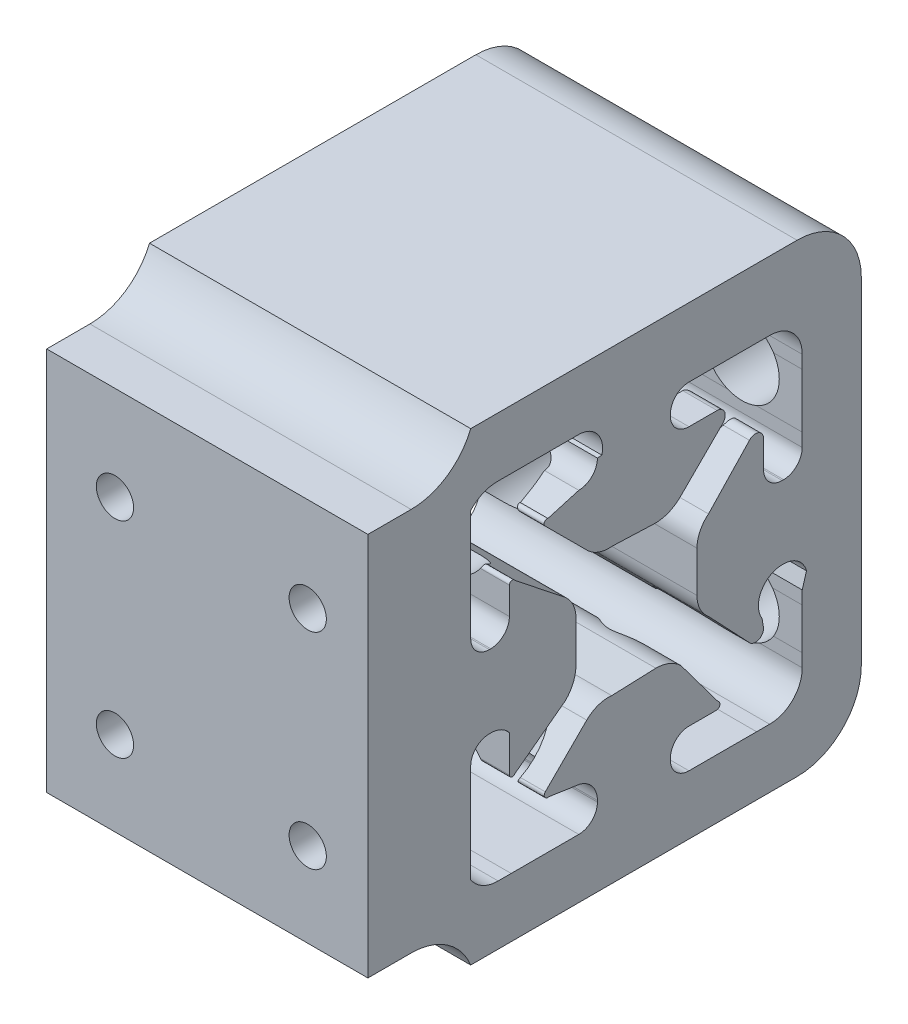
SolidWorks part; units mm, degrees
ref_plane "Front Plane" through (0, 0, 0) normal (0, 0, 1) x (1, 0, 0)
ref_plane "Top Plane" through (0, 0, 0) normal (0, 1, 0) x (1, 0, 0)
ref_plane "Right Plane" through (0, 0, 0) normal (1, 0, 0) x (0, 0, -1)
sketch "Sketch1" plane through (0, 0, 0) normal (0, 0, 1) x (1, 0, 0)
  line L1 (-7.5, -8) -> (7.5, -8) construction
  line L2 (-7.5, -8) -> (-7.5, 8) construction
  line L3 (-7.5, 8) -> (7.5, 8) construction
  line L4 (7.5, -8) -> (7.5, 8) construction
  line L5 (-7.5, -8) -> (7.5, 8) construction
  line L6 (-7.5, 8) -> (7.5, -8) construction
  line L7 (-12.8154, -14.5728) -> (12.1846, -14.5728)
  line L8 (-12.8154, -14.5728) -> (-12.8154, 15.3272)
  line L9 (-12.8154, 15.3272) -> (12.1846, 15.3272)
  line L10 (12.1846, -14.5728) -> (12.1846, 15.3272)
  line L11 (-12.8154, -14.5728) -> (12.1846, 15.3272) construction
  line L12 (-12.8154, 15.3272) -> (12.1846, -14.5728) construction
  circle A0 centre (-7.5, 8) radius 2.9
  circle A1 centre (7.5, 8) radius 2.9
  circle A2 centre (7.5, -8) radius 2.9
  circle A3 centre (-7.5, -8) radius 2.9
  point P0 (0, 0)
  point P6 (0, 0)
  dimension "D3" = 5.8
  dimension "D1" = 16
  dimension "D2" = 15
  dimension "D6" = 29.9
  dimension "D7" = 25
  dimension "D8" = 5.3154
  dimension "D4" = 2
  dimension "D5" = 2
extrude "Boss-Extrude1" add sketch "Sketch1" along normal blind 5
sketch "Sketch2" plane through (0, 0, 0) normal (1, 0, 0) x (0, 0, -1)
  line L0 (5.5203, -8.6452) -> (8.7477, -5.4237) construction
  line L1 (10.9895, -4.627) -> (14.4013, -4.4958) construction
  line L2 (16.6734, -5.445) -> (19.5306, -9.27) construction
  line L3 (19.1164, -10.4902) -> (16.9875, -10.4902) construction
  line L4 (15.9385, -11.5392) -> (15.9385, -11.651) construction
  line L5 (16.9875, -12.7) -> (18.0171, -12.7) construction
  line L6 (19.0331, -12.7) -> (22.2504, -12.7) construction
  line L7 (25.4, -9.5504) -> (25.4, -6.3331) construction
  line L8 (25.4, -5.2589) -> (25.7151, -4.1987) construction
  line L9 (24.351, -3.2385) -> (24.2392, -3.2385) construction
  line L10 (23.0637, -5.5347) -> (23.1538, -6.131) construction
  line L11 (21.4013, -7.0918) -> (18.2348, -3.7479) construction
  line L12 (17.2085, -1.5932) -> (17.2085, 1.5932) construction
  line L13 (18.2348, 3.7479) -> (21.4013, 7.0918) construction
  line L14 (23.1902, 6.4021) -> (23.1902, 4.2875) construction
  line L15 (24.2392, 3.2385) -> (24.351, 3.2385) construction
  line L16 (25.4, 4.2875) -> (25.4, 5.3171) construction
  line L17 (25.4, 6.3331) -> (25.4, 9.5504) construction
  line L18 (22.2504, 12.7) -> (19.0331, 12.7) construction
  line L19 (18.0171, 12.7) -> (16.9875, 12.7) construction
  line L20 (15.9385, 11.651) -> (15.9385, 11.5392) construction
  line L21 (16.9875, 10.4902) -> (19.1768, 10.4902) construction
  line L22 (19.907, 8.7244) -> (16.5983, 5.4232) construction
  line L23 (14.1125, 4.5051) -> (11.0428, 4.6269) construction
  line L24 (8.8017, 5.4232) -> (5.493, 8.7244) construction
  line L25 (5.9838, 9.8056) -> (8.3604, 10.4915) construction
  line L26 (9.3959, 11.9043) -> (9.86, 11.9403) construction
  line L27 (8.4125, 13.4545) -> (7.3829, 13.4545) construction
  line L28 (6.3669, 13.4545) -> (3.1497, 13.4545) construction
  line L31 (1.449, 3.2385) -> (1.5608, 3.2385) construction
  line L32 (2.6098, 4.2875) -> (2.6098, 6.4021) construction
  line L33 (3.7361, 6.7825) -> (7.54, 3.7681) construction
  line L34 (8.5915, 1.5932) -> (8.5915, -1.5932) construction
  line L35 (7.6385, -3.8611) -> (3.7076, -6.8173) construction
  line L36 (2.6098, -6.4021) -> (2.6098, -3.6879) construction
  line L37 (1.5608, -3.2385) -> (1.449, -3.2385) construction
  line L40 (3.1496, -12.7) -> (6.3669, -12.7) construction
  line L41 (7.3829, -12.7) -> (8.4125, -12.7) construction
  line L42 (9.4615, -11.651) -> (9.4615, -11.5392) construction
  line L43 (8.42, -10.1487) -> (6.0885, -9.8015) construction
  line L44 (0, 0) -> (36.6961, 0) construction
  line L45 (0, -14.5728) -> (0, 15.3272) construction
  line L46 (0, -14.5728) -> (0, -11.9507)
  line L47 (0, 15.3272) -> (0, 18.4545)
  line L48 (0, 18.4545) -> (30.4, 18.4545)
  line L49 (30.4, 18.4545) -> (30.4, -17.7)
  line L50 (30.4, -17.7) -> (0, -17.7)
  line L51 (0, -17.7) -> (0, -14.5728)
  line L53 (-0.4948, 12.1635) -> (0, 15.3272)
  line L54 (2.1336, -12.6998) -> (3.1496, -12.7) construction
  line L55 (2.1258, 13.4543) -> (3.1497, 13.4545) construction
  line L56 (6.3669, 13.4545) -> (7.3829, 13.4545) construction
  line L57 (18.0171, 12.7) -> (19.0331, 12.7) construction
  line L58 (22.2504, 12.7) -> (23.2664, 12.6998) construction
  line L59 (25.3998, 10.5664) -> (25.4, 9.5504) construction
  line L60 (25.4, 6.3331) -> (25.4, 5.3171) construction
  line L61 (6.3669, -12.7) -> (7.3829, -12.7) construction
  line L62 (18.0171, -12.7) -> (19.0331, -12.7) construction
  line L63 (23.2664, -12.6998) -> (22.2504, -12.7) construction
  line L64 (25.3998, -10.5664) -> (25.4, -9.5504) construction
  line L65 (25.4, -6.3331) -> (25.4, -5.2589) construction
  line L66 (2.1358, -13.0998) -> (3.1495, -13.1)
  line L67 (3.1495, -13.1) -> (6.3669, -13.1)
  line L68 (6.3669, -13.1) -> (7.3829, -13.1)
  line L69 (7.3829, -13.1) -> (8.4125, -13.1)
  line L70 (9.8615, -11.651) -> (9.8615, -11.5392)
  line L71 (8.5045, -9.7569) -> (6.0799, -9.3958)
  line L72 (5.8029, -8.9283) -> (9.0303, -5.7068)
  line L73 (10.9758, -5.0278) -> (14.4093, -4.8958)
  line L74 (16.3697, -5.7068) -> (19.2506, -9.5637)
  line L75 (19.1164, -10.0902) -> (16.9875, -10.0902)
  line L76 (15.5385, -11.5392) -> (15.5385, -11.651)
  line L77 (16.9875, -13.1) -> (18.0171, -13.1)
  line L78 (18.0171, -13.1) -> (19.0331, -13.1)
  line L79 (19.0331, -13.1) -> (22.2505, -13.1)
  line L80 (23.2642, -13.0998) -> (22.2505, -13.1)
  line L81 (25.7998, -10.5641) -> (25.8, -9.5504)
  line L82 (25.8, -9.5504) -> (25.8, -6.3331)
  line L83 (25.8, -6.3331) -> (25.8, -5.3171)
  line L84 (25.8, -5.3171) -> (26.1333, -4.1955)
  line L85 (24.351, -2.8385) -> (24.2392, -2.8385)
  line L86 (22.6817, -5.684) -> (22.7622, -6.2168)
  line L87 (21.6951, -6.8204) -> (18.5065, -3.4531)
  line L88 (17.6085, -1.5932) -> (17.6085, 1.5932)
  line L89 (18.5065, 3.4531) -> (21.6952, 6.8204)
  line L90 (22.7902, 6.4021) -> (22.7902, 4.2875)
  line L91 (24.2392, 2.8385) -> (24.351, 2.8385)
  line L92 (25.8, 4.2875) -> (25.8, 5.3171)
  line L93 (25.8, 6.3331) -> (25.8, 5.3171)
  line L94 (25.8, 6.3331) -> (25.8, 9.5504)
  line L95 (25.7998, 10.5641) -> (25.8, 9.5504)
  line L96 (22.2505, 13.1) -> (23.2642, 13.0998)
  line L97 (22.2505, 13.1) -> (19.0331, 13.1)
  line L98 (18.0171, 13.1) -> (19.0331, 13.1)
  line L99 (18.0171, 13.1) -> (16.9875, 13.1)
  line L100 (15.5385, 11.651) -> (15.5385, 11.5392)
  line L101 (16.9875, 10.0902) -> (19.1768, 10.0902)
  line L102 (19.6245, 9.0075) -> (16.3158, 5.7063)
  line L103 (14.136, 4.9045) -> (11.0293, 5.0278)
  line L104 (9.0842, 5.7063) -> (5.7755, 9.0075)
  line L105 (6.0096, 9.3967) -> (8.4125, 10.0902)
  line L106 (9.8615, 11.5392) -> (10.2085, 11.5661)
  line L107 (8.4125, 13.8545) -> (7.3829, 13.8545)
  line L108 (6.3669, 13.8545) -> (7.3829, 13.8545)
  line L109 (6.3669, 13.8545) -> (3.1497, 13.8545)
  line L110 (2.13, 13.8543) -> (3.1497, 13.8545)
  line L111 (1.449, 2.8385) -> (1.5608, 2.8385)
  line L112 (3.0098, 4.2875) -> (3.0098, 6.4021)
  line L113 (3.4384, 6.5081) -> (7.2916, 3.4546)
  line L114 (8.1915, 1.5932) -> (8.1915, -1.5932)
  line L115 (7.3765, -3.5577) -> (3.4264, -6.5283)
  line L116 (3.0098, -6.4021) -> (3.0098, -3.5389)
  line L117 (1.5608, -2.8385) -> (1.449, -2.8385)
  line L118 (0, 4.2875) -> (0, -4.2875)
  arc A1 (5.5203, -8.6452) -> (6.0885, -9.8015) centre (6.001, -9.1267) ccw construction
  arc A2 (10.9895, -4.627) -> (8.7477, -5.4237) centre (10.7082, -7.3877) ccw construction
  arc A3 (16.6734, -5.445) -> (14.4013, -4.4958) centre (14.4093, -7.6708) ccw construction
  arc A4 (19.1164, -10.4902) -> (19.5306, -9.27) centre (19.1164, -9.8098) ccw construction
  arc A5 (16.9875, -10.4902) -> (15.9385, -11.5392) centre (16.9875, -11.5392) ccw construction
  arc A6 (15.9385, -11.651) -> (16.9875, -12.7) centre (16.9875, -11.651) ccw construction
  arc A9 (23.2664, -12.6998) -> (25.3998, -10.5664) centre (23.2918, -10.5918) ccw construction
  arc A12 (25.7151, -4.1987) -> (24.351, -3.2385) centre (24.351, -4.6875) ccw construction
  arc A13 (24.2392, -3.2385) -> (23.0637, -5.5347) centre (24.2392, -4.6875) ccw construction
  arc A14 (21.4013, -7.0918) -> (23.1538, -6.131) centre (22.1628, -6.4021) ccw construction
  arc A15 (17.2085, -1.5932) -> (18.2348, -3.7479) centre (19.9835, -1.5932) ccw construction
  arc A16 (18.2348, 3.7479) -> (17.2085, 1.5932) centre (19.9835, 1.5932) ccw construction
  arc A17 (23.1902, 6.4021) -> (21.4013, 7.0918) centre (22.1628, 6.4021) ccw construction
  arc A18 (23.1902, 4.2875) -> (24.2392, 3.2385) centre (24.2392, 4.2875) ccw construction
  arc A19 (24.351, 3.2385) -> (25.4, 4.2875) centre (24.351, 4.2875) ccw construction
  arc A22 (25.3998, 10.5664) -> (23.2664, 12.6998) centre (23.2918, 10.5918) ccw construction
  arc A25 (16.9875, 12.7) -> (15.9385, 11.651) centre (16.9875, 11.651) ccw construction
  arc A26 (15.9385, 11.5392) -> (16.9875, 10.4902) centre (16.9875, 11.5392) ccw construction
  arc A27 (19.907, 8.7244) -> (19.1768, 10.4902) centre (19.1768, 9.4563) ccw construction
  arc A28 (14.1125, 4.5051) -> (16.5983, 5.4232) centre (14.3558, 7.6708) ccw construction
  arc A29 (8.8017, 5.4232) -> (11.0428, 4.6269) centre (10.7617, 7.3876) ccw construction
  arc A30 (5.9838, 9.8056) -> (5.493, 8.7244) centre (5.9407, 9.1731) ccw construction
  arc A31 (8.3604, 10.4915) -> (9.3959, 11.9043) centre (8.4125, 11.5392) ccw construction
  arc A32 (9.86, 11.9403) -> (8.4125, 13.4545) centre (8.4125, 12.0055) ccw construction
  arc A35 (2.1258, 13.4543) -> (0.5639, 9.1987) centre (2.0736, 11.0591) ccw construction
  arc A38 (0.4, 4.2875) -> (1.449, 3.2385) centre (1.449, 4.2875) ccw construction
  arc A39 (1.5608, 3.2385) -> (2.6098, 4.2875) centre (1.5608, 4.2875) ccw construction
  arc A40 (3.7361, 6.7825) -> (2.6098, 6.4021) centre (3.2372, 6.4021) ccw construction
  arc A41 (8.5915, 1.5932) -> (7.54, 3.7681) centre (5.8165, 1.5932) ccw construction
  arc A42 (7.6385, -3.8611) -> (8.5915, -1.5932) centre (5.4165, -1.5932) ccw construction
  arc A43 (2.6098, -6.4021) -> (3.7076, -6.8173) centre (3.2372, -6.4021) ccw construction
  arc A44 (2.6098, -3.6879) -> (1.5608, -3.2385) centre (1.5608, -4.6875) ccw construction
  arc A45 (1.449, -3.2385) -> (0.4, -4.2875) centre (1.449, -4.2875) ccw construction
  arc A48 (0.0002, -10.5664) -> (2.1336, -12.6998) centre (2.1082, -10.5918) ccw construction
  arc A51 (8.4125, -12.7) -> (9.4615, -11.651) centre (8.4125, -11.651) ccw construction
  arc A52 (9.4615, -11.5392) -> (8.42, -10.1487) centre (8.0125, -11.5392) ccw construction
  arc A53 (0, -11.9507) -> (2.1358, -13.0998) centre (2.1082, -10.5918) ccw
  arc A54 (8.4125, -13.1) -> (9.8615, -11.651) centre (8.4125, -11.651) ccw
  arc A55 (9.8615, -11.5392) -> (8.5045, -9.7569) centre (8.0125, -11.5392) ccw
  arc A56 (5.8029, -8.9283) -> (6.0799, -9.3958) centre (6.001, -9.1267) ccw
  arc A57 (10.9758, -5.0278) -> (9.0303, -5.7068) centre (10.7082, -7.3877) ccw
  arc A58 (16.3697, -5.7068) -> (14.4093, -4.8958) centre (14.4093, -7.6708) ccw
  arc A59 (19.1164, -10.0902) -> (19.2506, -9.5637) centre (19.1164, -9.8098) ccw
  arc A60 (16.9875, -10.0902) -> (15.5385, -11.5392) centre (16.9875, -11.5392) ccw
  arc A61 (15.5385, -11.651) -> (16.9875, -13.1) centre (16.9875, -11.651) ccw
  arc A62 (23.2642, -13.0998) -> (25.7998, -10.5641) centre (23.2918, -10.5918) ccw
  arc A63 (26.1333, -4.1955) -> (24.351, -2.8385) centre (24.351, -4.6875) ccw
  arc A64 (24.2392, -2.8385) -> (22.6817, -5.684) centre (24.2392, -4.6875) ccw
  arc A65 (21.6951, -6.8204) -> (22.7622, -6.2168) centre (22.1628, -6.4021) ccw
  arc A66 (17.6085, -1.5932) -> (18.5065, -3.4531) centre (19.9835, -1.5932) ccw
  arc A67 (18.5065, 3.4531) -> (17.6085, 1.5932) centre (19.9835, 1.5932) ccw
  arc A68 (22.7902, 6.4021) -> (21.6952, 6.8204) centre (22.1628, 6.4021) ccw
  arc A69 (22.7902, 4.2875) -> (24.2392, 2.8385) centre (24.2392, 4.2875) ccw
  arc A70 (24.351, 2.8385) -> (25.8, 4.2875) centre (24.351, 4.2875) ccw
  arc A71 (25.7998, 10.5641) -> (23.2642, 13.0998) centre (23.2918, 10.5918) ccw
  arc A72 (16.9875, 13.1) -> (15.5385, 11.651) centre (16.9875, 11.651) ccw
  arc A73 (15.5385, 11.5392) -> (16.9875, 10.0902) centre (16.9875, 11.5392) ccw
  arc A74 (19.6245, 9.0075) -> (19.1768, 10.0902) centre (19.1768, 9.4563) ccw
  arc A75 (14.136, 4.9045) -> (16.3158, 5.7063) centre (14.3558, 7.6708) ccw
  arc A76 (9.0842, 5.7063) -> (11.0293, 5.0278) centre (10.7617, 7.3876) ccw
  arc A77 (6.0096, 9.3967) -> (5.7755, 9.0075) centre (5.9407, 9.1731) ccw
  arc A78 (8.4125, 10.0902) -> (9.8615, 11.5392) centre (8.4125, 11.5392) ccw
  arc A79 (10.2085, 11.5661) -> (8.4125, 13.8545) centre (8.4125, 12.0055) ccw
  arc A80 (2.13, 13.8543) -> (-0.4948, 12.1635) centre (2.0736, 11.0591) ccw
  arc A81 (0, 4.2875) -> (1.449, 2.8385) centre (1.449, 4.2875) ccw
  arc A82 (1.5608, 2.8385) -> (3.0098, 4.2875) centre (1.5608, 4.2875) ccw
  arc A83 (3.4384, 6.5081) -> (3.0098, 6.4021) centre (3.2372, 6.4021) ccw
  arc A84 (8.1915, 1.5932) -> (7.2916, 3.4546) centre (5.8165, 1.5932) ccw
  arc A85 (7.3765, -3.5577) -> (8.1915, -1.5932) centre (5.4165, -1.5932) ccw
  arc A86 (3.0098, -6.4021) -> (3.4264, -6.5283) centre (3.2372, -6.4021) ccw
  arc A87 (3.0098, -3.5389) -> (1.5608, -2.8385) centre (1.5608, -4.6875) ccw
  arc A88 (1.449, -2.8385) -> (0, -4.2875) centre (1.449, -4.2875) ccw
  arc A89 (-0.3998, -10.5616) -> (2.1358, -13.0998) centre (2.1082, -10.5918) ccw construction
  arc A90 (2.13, 13.8543) -> (0.3119, 8.8881) centre (2.0736, 11.0591) ccw construction
  point P153 (8.5915, 0)
  point P160 (30.4, 18.4545)
  dimension "D1" = 0
  dimension "D2" = 0.4
  dimension "D3" = 1.8728
  dimension "D4" = 3.1272
  dimension "D6" = 5
  dimension "D7" = 25.4
  dimension "D8" = 5
extrude "Boss-Extrude2" add sketch "Sketch2" along normal up to surface and the other way up to surface contours L12 L44 L49 L48 L47 L53 A35 L55 L28 L56 L27 A32 L26 A31 L25 A30 L24 A29 L23 A28 L22 A27 L21 A26 L20 A25 L19 L57 L18 L58 A22 L59 L17 L60 L16 A19 L15 A18 L14 A17 L13 A16 | L44 L12 A15 L11 A14 L10 A13 L9 A12 L8 L65 L7 L64 A9 L63 L6 L62 L5 A6 L4 A5 L3 A4 L2 A3 L1 A2 L0 A1 L43 A52 L42 A51 L41 L61 L40 L54 A48 L46 L51 L50 L49 | L44 A45 L37 A44 L36 A43 L35 A42 L34 | L44 L34 A41 L33 A40 L32 A39 L31 A38 | L118 A88 L117 A87 L116 A86 L115 A85 L114 A84 L113 A83 L112 A82 L111 A81 region at (0, 0.5364, -17.9373) up to face at (12.1846, 0.3772, 2.5) other way up to face at (-12.8154, 0.3772, 2.5)
fillet "Fillet1" radius 5 4 edges at (-0.3154, -14.5728, 0) (-0.3154, -17.7, -30.4) (-0.3154, 18.4545, -30.4) (-0.3154, 15.3272, 0)
sketch "Sketch5" plane through (0, 0, 5) normal (0, 0, 1) x (1, 0, 0)
  circle A0 centre (-7.5, -8) radius 2.9 construction
  circle A1 centre (7.5, -8) radius 2.9 construction
  circle A2 centre (7.5, 8) radius 2.9 construction
  circle A3 centre (-7.5, 8) radius 2.9 construction
  circle A8 centre (-7.5, -8) radius 2.9
  circle A9 centre (7.5, -8) radius 2.9
  circle A10 centre (7.5, 8) radius 2.9
  circle A11 centre (-7.5, 8) radius 2.9
extrude "Cut-Extrude1" cut sketch "Sketch5" against normal through all
sketch "Sketch6" plane through (0, 0, 5) normal (0, 0, 1) x (1, 0, 0)
  line L4 (12.1846, -14.5728) -> (12.1846, 15.3272)
  line L5 (12.1846, 15.3272) -> (-12.8154, 15.3272)
  line L6 (-12.8154, 15.3272) -> (-12.8154, -14.5728)
  line L7 (-12.8154, -14.5728) -> (12.1846, -14.5728)
  line L8 (12.1846, -14.5728) -> (12.1846, 15.3272)
  line L9 (12.1846, 15.3272) -> (-12.8154, 15.3272)
  line L10 (-12.8154, 15.3272) -> (-12.8154, -14.5728)
  line L11 (-12.8154, -14.5728) -> (12.1846, -14.5728)
  circle A0 centre (-7.5, -8) radius 2.9 construction
  circle A1 centre (7.5, -8) radius 2.9 construction
  circle A2 centre (7.5, 8) radius 2.9 construction
  circle A3 centre (-7.5, 8) radius 2.9 construction
  circle A4 centre (-7.5, -8) radius 2.9 construction
  circle A5 centre (7.5, -8) radius 2.9 construction
  circle A6 centre (7.5, 8) radius 2.9 construction
  circle A7 centre (-7.5, 8) radius 2.9 construction
  circle A8 centre (-7.5, 8) radius 1.45
  circle A9 centre (7.5, 8) radius 1.45
  circle A10 centre (7.5, -8) radius 1.45
  circle A11 centre (-7.5, -8) radius 1.45
  dimension "D1" = 2.9
  dimension "D4" = 16
  dimension "D5" = 15
  dimension "D7" = 5.3154
  dimension "D6" = 0
  dimension "D2" = 2
  dimension "D3" = 2
extrude "Boss-Extrude3" add sketch "Sketch6" along normal blind 3
sketch "Sketch9" plane through (0, -17.7, 0) normal (0, -1, 0) x (1, 0, 0)
  line L0 (-12.8154, 8) -> (12.1846, 8) construction
  line L1 (12.1846, -30.4) -> (-12.8154, -30.4) construction
  line L2 (-12.8154, 8) -> (11.325, 8)
  line L3 (11.325, -30.4) -> (-12.8154, -30.4)
  line L4 (11.325, -30.4) -> (11.325, 8)
  line L5 (-12.8154, -30.4) -> (-12.8154, 8)
extrude "Cut-Extrude3" [suppressed] cut sketch "Sketch9" against normal blind 38
